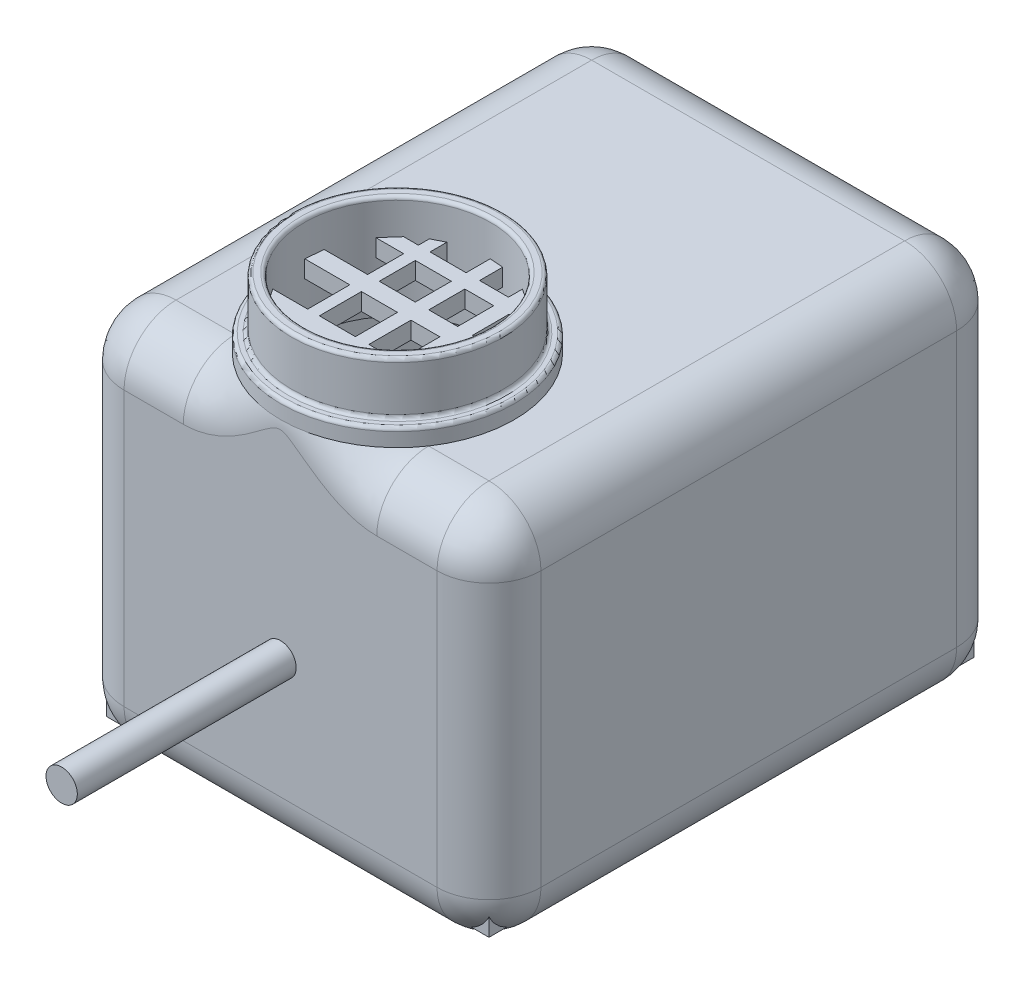
SolidWorks part; units mm, degrees
ref_plane "Front Plane" through (0, 0, 0) normal (0, 0, 1) x (1, 0, 0)
ref_plane "Top Plane" through (0, 0, 0) normal (0, 1, 0) x (1, 0, 0)
ref_plane "Right Plane" through (0, 0, 0) normal (1, 0, 0) x (0, 0, -1)
sketch "Sketch1" plane through (0, 0, 0) normal (0, 0, 1) x (1, 0, 0)
  line L1 (7.5, 12.5) -> (-7.5, 12.5)
  line L2 (7.5, 12.5) -> (7.5, -12.5)
  line L3 (7.5, -12.5) -> (-7.5, -12.5)
  line L4 (-7.5, 12.5) -> (-7.5, -12.5)
  line L5 (7.5, 12.5) -> (-7.5, -12.5) construction
  line L6 (7.5, -12.5) -> (-7.5, 12.5) construction
  point P0 (0, 0)
  dimension "D1" = 25
  dimension "D2" = 15
extrude "Boss-Extrude1" add sketch "Sketch1" along normal blind 30
sketch "Sketch2" plane through (0, 0, 0) normal (0, 0, -1) x (-1, 0, 0)
  line L0 (-7.5, -12.5) -> (7.5, -12.5)
  line L1 (7.5, -12.5) -> (7.5, -20.0971)
  line L2 (7.5, -20.0971) -> (-7.5, -20.0971)
  line L3 (-7.5, -20.0971) -> (-7.5, -12.5)
extrude "Boss-Extrude2" add sketch "Sketch2" against normal blind 1
ref_plane "Plane1" through (0, 0, 6) normal (0, 0, 1) x (1, 0, 0)
sketch "Sketch3" plane through (0, 0, 6) normal (0, 0, 1) x (1, 0, 0)
  line L0 (7.5, -12.5) -> (7.5, -20.0971)
  line L1 (7.5, -20.0971) -> (-7.5, -20.0971)
  line L2 (-7.5, -20.0971) -> (-7.5, -12.5)
  line L3 (-7.5, -12.5) -> (7.5, -12.5)
extrude "Boss-Extrude3" add sketch "Sketch3" along normal blind 1
sketch "Sketch4" plane through (7.5, 0, 0) normal (1, 0, 0) x (0, 0, -1)
  line L0 (0, 4.1708) -> (-19.4092, 4.1708)
  line L1 (0, -20.0971) -> (0, 12.5) construction
  line L2 (-19.4092, 4.1708) -> (-19.4092, -12.5)
  line L3 (-30, -12.5) -> (-7, -12.5) construction
  line L4 (-19.4092, -12.5) -> (-30, -12.5)
  line L5 (-30, -12.5) -> (-30, 12.5)
  line L6 (-30, 12.5) -> (0, 12.5)
  line L7 (0, 12.5) -> (0, 4.1708)
extrude "Cut-Extrude1" cut sketch "Sketch4" against normal blind 33
sketch "Sketch5" plane through (0, 0, 0) normal (0, 0, -1) x (-1, 0, 0)
  line L0 (-7.5083, -12.0431) -> (7.4404, -12.0431)
  line L1 (7.4404, -12.0431) -> (-7.5, 4.1708)
  circle A0 centre (-0.0298, -3.9362) radius 0.9044
extrude "Boss-Extrude4" add sketch "Sketch5" along normal blind 15 contours L1 A0 | L1 A0 region at (0.3121, -4.1963, 0) region at (-0.2525, -3.6761, 0)
sketch "Sketch6" plane through (0, 0, -15) normal (0, 0, -1) x (-1, 0, 0)
  line L1 (12.0069, 5.9788) -> (-12.0665, 5.9788)
  line L2 (12.0069, 5.9788) -> (12.0069, -13.8511)
  line L3 (12.0069, -13.8511) -> (-12.0665, -13.8511)
  line L4 (-12.0665, 5.9788) -> (-12.0665, -13.8511)
  line L5 (12.0069, 5.9788) -> (-12.0665, -13.8511) construction
  line L6 (12.0069, -13.8511) -> (-12.0665, 5.9788) construction
  point P0 (-0.0298, -3.9362)
extrude "Boss-Extrude5" add sketch "Sketch6" along normal blind 30
shell "Shell1" thickness 1 removed face at (0.0298, 5.9788, -30)
fillet "Fillet1" radius 3 8 edges at (-12.0069, -13.8511, -30) (0.0298, -13.8511, -45) (0.0298, -13.8511, -15) (12.0665, -13.8511, -30) (12.0665, -3.9362, -15) (-12.0069, -3.9362, -45) (12.0665, -3.9362, -45) (-12.0069, -3.9362, -15)
sketch "Sketch7" plane through (0, 5.9788, 0) normal (0, 1, 0) x (1, 0, 0)
  line L4 (-9.0069, 15) -> (9.0665, 15)
  line L5 (12.0665, 18) -> (12.0665, 42)
  line L6 (9.0665, 45) -> (-9.0069, 45)
  line L7 (-12.0069, 42) -> (-12.0069, 18)
  line L8 (-9.0069, 15) -> (9.0665, 15)
  line L9 (12.0665, 18) -> (12.0665, 42)
  line L10 (9.0665, 45) -> (-9.0069, 45)
  line L11 (-12.0069, 42) -> (-12.0069, 18)
  circle A0 centre (0, 21.7825) radius 5.385
  arc A4 (9.0665, 15) -> (12.0665, 18) centre (9.0665, 18) ccw
  arc A5 (12.0665, 42) -> (9.0665, 45) centre (9.0665, 42) ccw
  arc A6 (-9.0069, 45) -> (-12.0069, 42) centre (-9.0069, 42) ccw
  arc A7 (-12.0069, 18) -> (-9.0069, 15) centre (-9.0069, 18) ccw
  arc A8 (9.0665, 15) -> (12.0665, 18) centre (9.0665, 18) ccw
  arc A9 (12.0665, 42) -> (9.0665, 45) centre (9.0665, 42) ccw
  arc A10 (-9.0069, 45) -> (-12.0069, 42) centre (-9.0069, 42) ccw
  arc A11 (-12.0069, 18) -> (-9.0069, 15) centre (-9.0069, 18) ccw
  dimension "D1" = 0
extrude "Boss-Extrude6" add sketch "Sketch7" along normal blind 2
sketch "Sketch8" plane through (0, 7.9788, 0) normal (0, 1, 0) x (1, 0, 0)
  circle A0 centre (0, 21.7825) radius 6.7461
extrude "Boss-Extrude7" add sketch "Sketch8" along normal blind 1
sketch "Sketch9" plane through (0, 8.9788, 0) normal (0, 1, 0) x (1, 0, 0)
  line L0 (3.6045, 25.7436) -> (3.3145, 25.7436)
  line L1 (-3.6045, 25.7436) -> (-4.3595, 24.8933)
  line L2 (-4.3595, 24.8933) -> (-2.7538, 24.8933)
  line L3 (4.3595, 24.8933) -> (3.6045, 25.7436)
  line L4 (5.2562, 22.8094) -> (3.3145, 22.8094)
  line L5 (-5.2562, 22.8094) -> (-5.3556, 21.7825)
  line L6 (-5.3556, 21.7825) -> (-2.7538, 21.7825)
  line L7 (5.3556, 21.7825) -> (5.2562, 22.8094)
  line L8 (4.8045, 19.3506) -> (3.3145, 19.3506)
  line L9 (-4.7716, 19.3506) -> (-4.0047, 18.2265)
  line L10 (-4.0047, 18.2265) -> (-2.7538, 18.2265)
  line L11 (4.0047, 18.2265) -> (4.8045, 19.3506)
  line L12 (0.7789, 27.0812) -> (0.7789, 25.7436)
  line L13 (0.7789, 16.4839) -> (0, 16.4269)
  line L14 (0, 16.4269) -> (0, 18.2265)
  line L15 (0, 27.1381) -> (0.7789, 27.0812)
  line L16 (-2.0798, 26.7178) -> (-2.0798, 25.7436)
  line L17 (-2.0798, 16.8473) -> (-2.7538, 17.1892)
  line L18 (-2.7538, 17.1892) -> (-2.7538, 18.2265)
  line L19 (-2.7538, 26.3759) -> (-2.0798, 26.7178)
  line L24 (2.4462, 26.5468) -> (2.4462, 25.7436)
  line L25 (2.4462, 17.0182) -> (3.3145, 17.5758)
  line L26 (3.3145, 17.5758) -> (3.3145, 18.2265)
  line L27 (3.3145, 25.9892) -> (2.4462, 26.5468)
  line L32 (3.3145, 25.7436) -> (3.3145, 25.9892)
  line L33 (2.4462, 25.7436) -> (0.7789, 25.7436)
  line L34 (-4.2933, 19.3506) -> (-4.7716, 19.3506)
  line L35 (2.4462, 24.8933) -> (2.4462, 22.8094)
  line L36 (3.3145, 24.8933) -> (4.3595, 24.8933)
  line L37 (3.3145, 22.8094) -> (3.3145, 24.8933)
  line L38 (2.4462, 21.7825) -> (2.4462, 19.3506)
  line L39 (2.4462, 22.8094) -> (0.7789, 22.8094)
  line L40 (3.3145, 21.7825) -> (5.3556, 21.7825)
  line L41 (3.3145, 19.3506) -> (3.3145, 21.7825)
  line L42 (3.3145, 18.2265) -> (4.0047, 18.2265)
  line L43 (2.4462, 18.2265) -> (2.4462, 17.0182)
  line L44 (2.4462, 19.3506) -> (0.7789, 19.3506)
  line L45 (0.7789, 18.2265) -> (0.7789, 16.4839)
  line L46 (0, 19.3506) -> (-2.0798, 19.3506)
  line L47 (0.7789, 18.2265) -> (2.4462, 18.2265)
  line L48 (0, 19.3506) -> (0, 21.7825)
  line L49 (-2.0798, 18.2265) -> (-2.0798, 16.8473)
  line L50 (-2.7538, 19.3506) -> (-4.7716, 19.3506)
  line L51 (-2.7538, 19.3506) -> (-2.7538, 21.7825)
  line L52 (-2.0798, 18.2265) -> (0, 18.2265)
  line L53 (-2.0798, 21.7825) -> (-2.0798, 19.3506)
  line L54 (-2.7538, 22.8094) -> (-5.2562, 22.8094)
  line L55 (-2.7538, 22.8094) -> (-2.7538, 24.8933)
  line L56 (-2.0798, 21.7825) -> (0, 21.7825)
  line L57 (0.7789, 21.7825) -> (0.7789, 19.3506)
  line L58 (0, 22.8094) -> (-2.0798, 22.8094)
  line L59 (0.7789, 21.7825) -> (2.4462, 21.7825)
  line L60 (0, 22.8094) -> (0, 24.8933)
  line L61 (0.7789, 24.8933) -> (2.4462, 24.8933)
  line L62 (0.7789, 24.8933) -> (0.7789, 22.8094)
  line L63 (0, 25.7436) -> (-2.0798, 25.7436)
  line L64 (0, 25.7436) -> (0, 27.1381)
  line L65 (-2.0798, 24.8933) -> (0, 24.8933)
  line L66 (-2.7538, 25.7436) -> (-3.6045, 25.7436)
  line L67 (-2.7538, 25.7436) -> (-2.7538, 26.3759)
  line L68 (-2.0798, 24.8933) -> (-2.0798, 22.8094)
  circle A1 centre (0, 21.7825) radius 5.385 construction
extrude "Boss-Extrude10" add sketch "Sketch9" along normal blind 1 separate body contours L67 L66 L1 L2 L55 L54 L5 L6 L51 L50 L34 L9 L10 L18 L17 L49 L52 L14 L13 L45 L47 L43 L25 L26 L42 L11 L8 L41 L40 L7 L4 L37 L36 L3 L0 L32 L27 L24 L33 L12 L15 L64 L63 L16 L19 L68 L65 L60 L58 region at (0.1544, 8.9788, -21.7736)
sketch "Sketch10" plane through (0, 8.9788, 0) normal (0, 1, 0) x (1, 0, 0)
  circle A0 centre (0, 21.7825) radius 5.385 construction
  circle A3 centre (0, 21.7825) radius 5.385
extrude "Cut-Extrude2" cut sketch "Sketch10" against normal blind 11
sketch "Sketch11" plane through (0, 8.9788, 0) normal (0, 1, 0) x (1, 0, 0)
  circle A0 centre (0, 21.7825) radius 5.385
  circle A1 centre (0, 21.7825) radius 6.1056
extrude "Boss-Extrude11" add sketch "Sketch11" along normal blind 3
fillet "Fillet2" radius 3 8 edges at (-11.1282, 7.9788, -44.1213) (0.0298, 7.9788, -45) (11.1878, 7.9788, -44.1213) (12.0665, 7.9788, -30) (11.1878, 7.9788, -15.8787) (0.0298, 7.9788, -15) (-11.1282, 7.9788, -15.8787) (-12.0069, 7.9788, -30)
fillet "Fillet3" radius 0.2 4 edges at (0, 8.9788, -15.677) (0, 11.9788, -16.3976) (0, 11.9788, -15.677) (0, 8.9788, -15.0364)
fillet "Fillet4" radius 1 13 edges at (-7.5, -16.2985, 7) (7.5, -16.2985, 7) (0, -20.0971, 7) (0, -12.5, 19.4092) (7.5, -4.1646, 19.4092) (-7.5, -4.1646, 19.4092) (7.5, -7.9631, 0) (0, -20.0971, 0) (-7.5, -7.9631, 0) (0, 4.1708, 19.4092) (7.5, 4.1708, 9.7046) (0, 4.1708, 0) (-7.5, 4.1708, 9.7046)
sketch "Sketch12" plane through (0, 0, 7) normal (0, 0, 1) x (1, 0, 0)
  line L1 (-0.7307, -16.9767) -> (0.7582, -16.9609)
  line L2 (0.7582, -16.9609) -> (1.4889, -15.6635)
  line L3 (1.4889, -15.6635) -> (0.7307, -14.382)
  line L4 (0.7307, -14.382) -> (-0.7582, -14.3978)
  line L5 (-0.7582, -14.3978) -> (-1.4889, -15.6952)
  line L6 (-1.4889, -15.6952) -> (-0.7307, -16.9767)
  circle A0 centre (0, -15.6793) radius 1.2895 construction
extrude "Boss-Extrude12" add sketch "Sketch12" along normal blind 1
sketch "Sketch13" plane through (0, 0, 8) normal (0, 0, 1) x (1, 0, 0)
  circle A0 centre (0, -15.6275) radius 0.6395
extrude "Boss-Extrude13" add sketch "Sketch13" along normal blind 5
sketch "Sketch14" plane through (0, 0, 13) normal (0, 0, 1) x (1, 0, 0)
  line L1 (-0.8844, -17.1379) -> (0.8659, -17.1486)
  line L2 (0.8659, -17.1486) -> (1.7503, -15.6382)
  line L3 (1.7503, -15.6382) -> (0.8844, -14.117)
  line L4 (0.8844, -14.117) -> (-0.8659, -14.1063)
  line L5 (-0.8659, -14.1063) -> (-1.7503, -15.6167)
  line L6 (-1.7503, -15.6167) -> (-0.8844, -17.1379)
  circle A0 centre (0, -15.6275) radius 1.5158 construction
extrude "Boss-Extrude14" add sketch "Sketch14" along normal blind 1
sketch "Sketch15" plane through (12.0665, 0, 0) normal (1, 0, 0) x (0, 0, -1)
  line L0 (2.3621, 17.6699) -> (-21.7541, 17.6699)
  line L1 (-21.7541, 17.6699) -> (-21.7541, -23.1495)
  line L2 (-21.7541, -23.1495) -> (2.3621, -23.1495)
  line L3 (2.3621, -23.1495) -> (2.3621, 17.6699)
extrude "Cut-Extrude5" cut sketch "Sketch15" against normal blind 68
